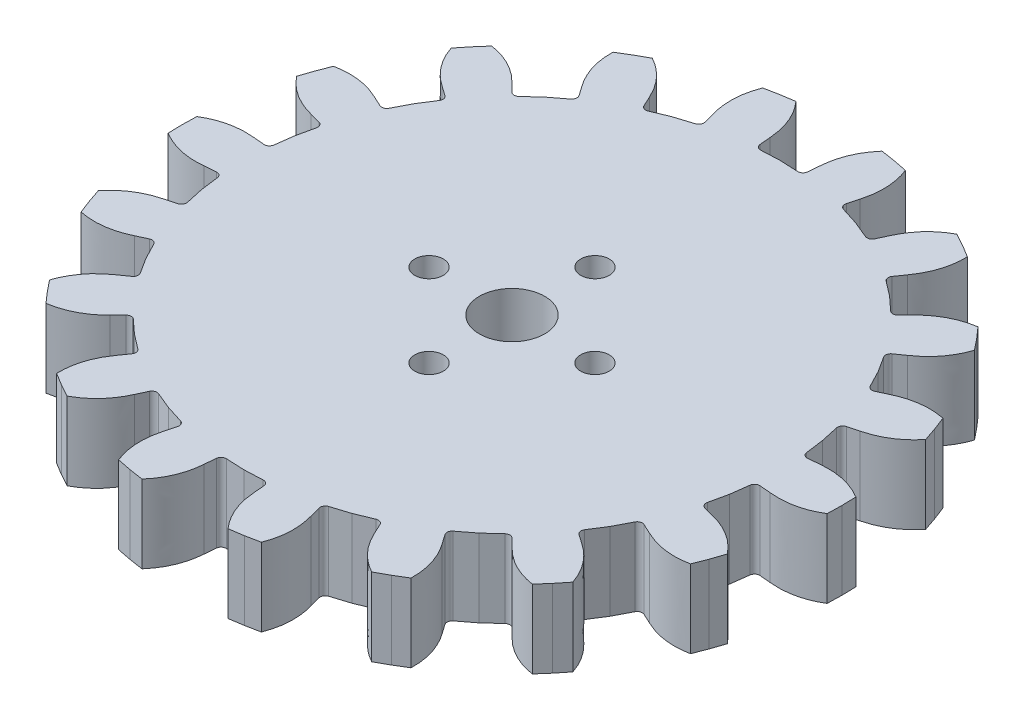
SolidWorks part; units mm, degrees
ref_plane "Front Plane" through (0, 0, 0) normal (0, 0, 1) x (1, 0, 0)
ref_plane "Top Plane" through (0, 0, 0) normal (0, 1, 0) x (1, 0, 0)
ref_plane "Right Plane" through (0, 0, 0) normal (1, 0, 0) x (0, 0, -1)
sketch "Sketch2" plane through (0, 0, 0) normal (0, 1, 0) x (1, 0, 0)
  line L0 (0, 0) -> (-45.4276, 0) construction
  line L1 (0, 0) -> (-44.5139, 1.9435) construction
  line L2 (0, 0) -> (-43.3229, 3.7903) construction
  line L3 (0, 0) -> (-25.445, 4.4866) construction
  line L4 (-25.7392, 2.2519) -> (-27.2858, 2.3872)
  line L5 (-25.7392, 2.2519) -> (-25.445, 4.4866)
  line L6 (-25.445, 4.4866) -> (0, 0)
  line L7 (-31.7697, 1.3871) -> (-31.8, 0)
  line L8 (-25.445, -4.4866) -> (0, 0)
  line L9 (-25.7392, -2.2519) -> (-25.445, -4.4866)
  line L10 (-25.7392, -2.2519) -> (-27.2858, -2.3872)
  line L11 (-31.7697, -1.3871) -> (-31.8, 0)
  circle A0 centre (0, 0) radius 25.8375 construction
  circle A1 centre (0, 0) radius 27.39 construction
  circle A2 centre (0, 0) radius 31.8 construction
  spline S0 degree 2 poles (-27.2858, 2.3872) (-29.7333, 2.6318) (-31.7697, 1.3871) knots 0 0 0 1 1 1
  spline S1 degree 2 poles (-27.2858, -2.3872) (-29.7333, -2.6318) (-31.7697, -1.3871) knots 0 0 0 1 1 1
  dimension "D1" = 63.6
  dimension "D2" = 54.78
  dimension "D3" = 51.675
  dimension "D4" = 2.5
  dimension "D5" = 10
  dimension "D6" = 5
extrude "Boss-Extrude1" add sketch "Sketch2" along normal blind 7.5
fillet "Fillet1" radius 0.5 2 edges at (-25.7392, 3.75, -2.2519) (-25.7392, 3.75, 2.2519)
pattern_circular "CirPattern1" count 18 over 360 about axis through (0, 7.5, 0) along (0, -1, 0) of "Boss-Extrude1", "Fillet1" reverse direction yes
sketch "Sketch3" plane through (0, 7.5, 0) normal (0, 1, 0) x (1, 0, 0)
  line L0 (0, 0) -> (-15.2674, 0) construction
  circle A0 centre (0, 0) radius 3.15
  circle A1 centre (-8, 0) radius 1.375
  circle A2 centre (0, 8) radius 1.375
  circle A3 centre (8, 0) radius 1.375
  circle A4 centre (0, -8) radius 1.375
  point P15 (0, 0)
  dimension "D1" = 6.3
  dimension "D3" = 2.75
  dimension "D2" = 8
  dimension "D4" = 4
extrude "Cut-Extrude1" cut sketch "Sketch3" against normal through all
